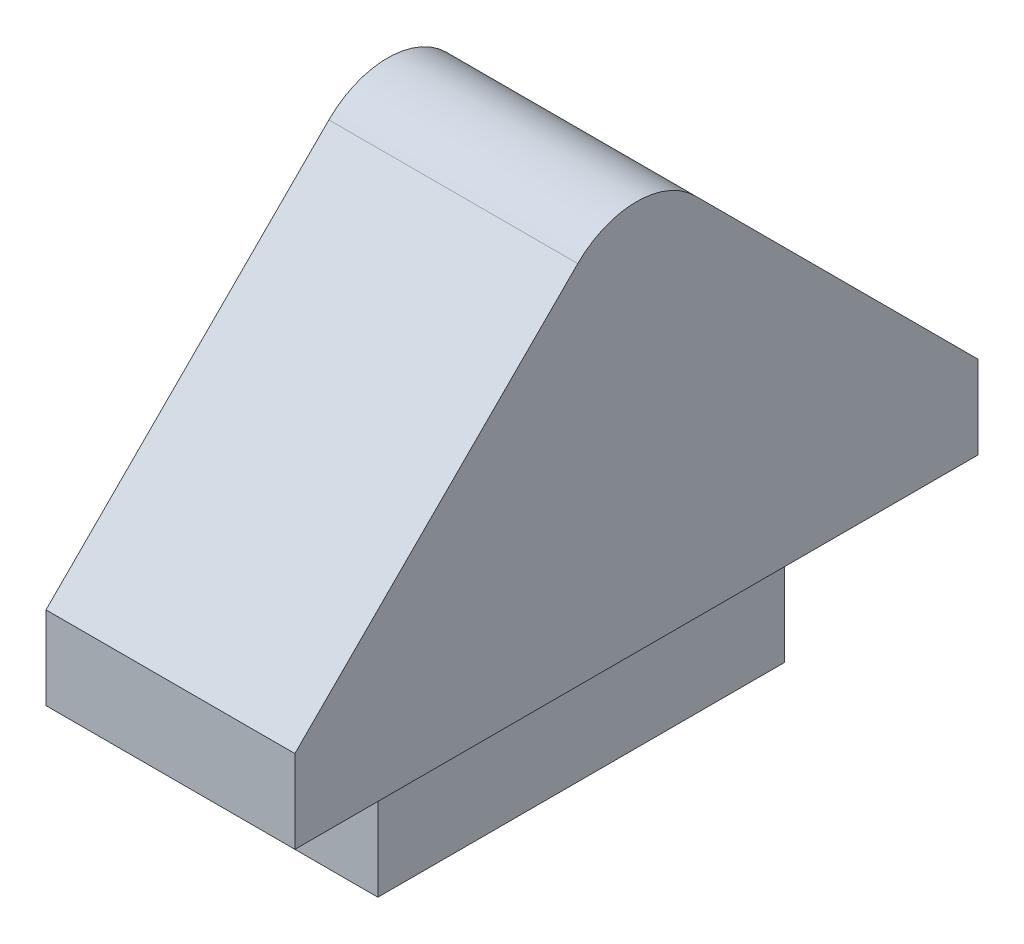
SolidWorks part; units mm, degrees
ref_plane "Front Plane" through (0, 0, 0) normal (0, 0, 1) x (1, 0, 0)
ref_plane "Top Plane" through (0, 0, 0) normal (0, 1, 0) x (1, 0, 0)
ref_plane "Right Plane" through (0, 0, 0) normal (1, 0, 0) x (0, 0, -1)
sketch "Sketch1" plane through (0, 0, 0) normal (0, 1, 0) x (1, 0, 0)
  line L1 (0, 0) -> (5, 0)
  line L2 (0, 0) -> (0, 14.7)
  line L3 (0, 14.7) -> (5, 14.7)
  line L4 (5, 0) -> (5, 14.7)
  dimension "D1" = 14.7
  dimension "D2" = 5
extrude "Boss-Extrude1" add sketch "Sketch1" along normal blind 5
sketch "Sketch2" plane through (0, 5, 0) normal (0, 1, 0) x (1, 0, 0)
  line L0 (5, 14.7) -> (0, 14.7) construction
  line L1 (-2, -5) -> (7, -5)
  line L2 (-2, -5) -> (-2, 19.7)
  line L3 (-2, 19.7) -> (7, 19.7)
  line L4 (7, -5) -> (7, 19.7)
  line L5 (0, 14.7) -> (0, 0) construction
  point P6 (2.5, 14.7)
  point P7 (2.5, 19.7)
  point P10 (0, 7.35)
  point P11 (-2, 7.35)
  dimension "D1" = 2
  dimension "D2" = 5
extrude "Boss-Extrude2" add sketch "Sketch2" along normal blind 3
sketch "Sketch3" plane through (7, 0, 0) normal (1, 0, 0) x (0, 0, -1)
  line L0 (-5, 8) -> (5.2287, 18.2287)
  line L1 (9.4713, 18.2287) -> (19.7, 8)
  line L2 (-5, 8) -> (19.7, 8) construction
  line L3 (-5, 8) -> (19.7, 8)
  arc A0 (5.2287, 18.2287) -> (9.4713, 18.2287) centre (7.35, 16.1074) cw
  point P3 (7.35, 8)
  point P7 (8.8816, 20.8914)
  point P9 (7.35, 21.0629)
  point P12 (7.35, 20.35)
  dimension "D2" = 3
  dimension "D1" = 90
extrude "Boss-Extrude3" add sketch "Sketch3" against normal up to surface (9 mm away) up to face at (-2, 6.5, -7.35)
